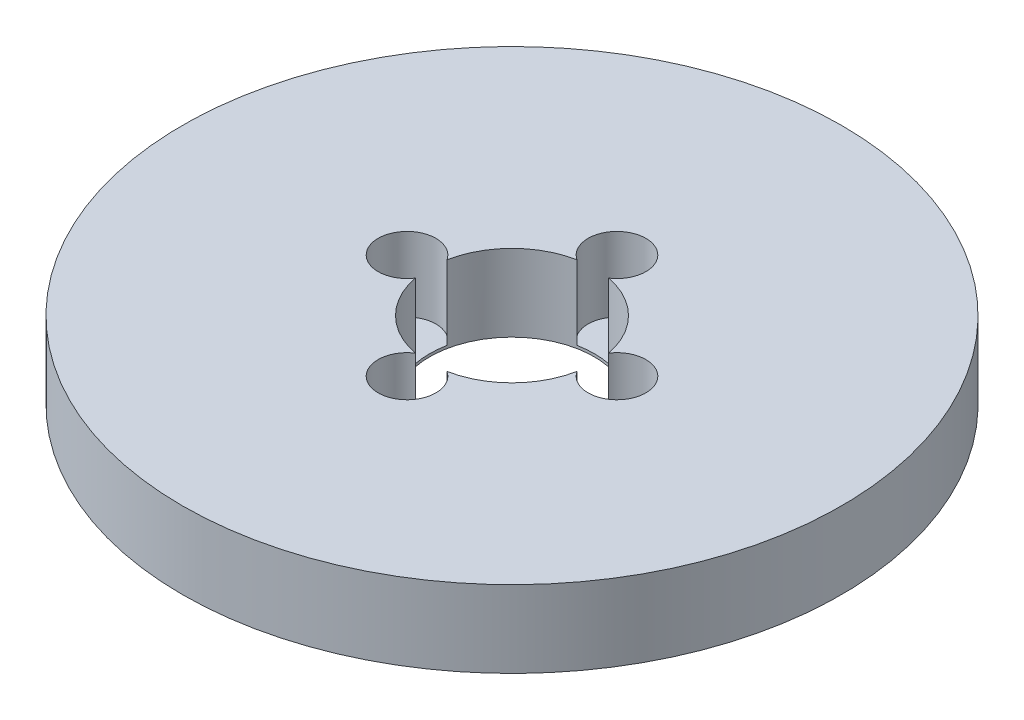
SolidWorks part; units mm, degrees
ref_plane "Front Plane" through (0, 0, 0) normal (0, 0, 1) x (1, 0, 0)
ref_plane "Top Plane" through (0, 0, 0) normal (0, 1, 0) x (1, 0, 0)
ref_plane "Right Plane" through (0, 0, 0) normal (1, 0, 0) x (0, 0, -1)
sketch "Sketch1" plane through (0, 0, 0) normal (0, 1, 0) x (1, 0, 0)
  circle A0 centre (0, 0) radius 30
  dimension "FLANGE_OD" = 60
extrude "Boss-Extrude1" add sketch "Sketch1" along normal blind 7
sketch "Sketch2" plane through (0, 0, 0) normal (0, 1, 0) x (1, 0, 0)
  circle A0 centre (0, 0) radius 7.5
  dimension "BORE_D" = 15
extrude "Cut-Extrude1" cut sketch "Sketch2" along normal through all
sketch "Sketch3" plane through (0, 7, 0) normal (0, 1, 0) x (1, 0, 0)
  circle A0 centre (0, 0) radius 9.5574 construction
  circle A1 centre (-9.5574, 0) radius 2.6294
  dimension "BOLT_D" = 5.2589
  dimension "BOLT_PCD" = 19.1147
extrude "Cut-Extrude2" cut sketch "Sketch3" against normal blind 6.752
pattern_circular "CirPattern1" count 4 over 360 about axis through (0, 0, 0) along (0, 1, 0) of "Cut-Extrude2"
